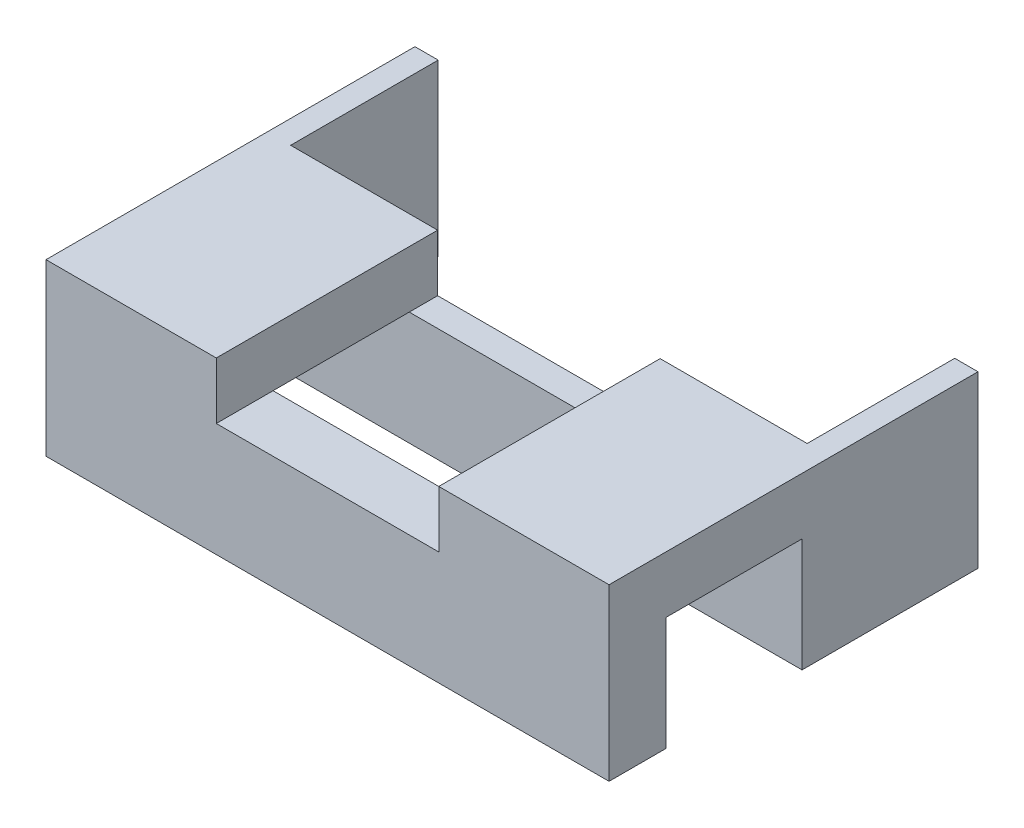
SolidWorks part; units mm, degrees
ref_plane "Front Plane" through (0, 0, 0) normal (0, 0, 1) x (1, 0, 0)
ref_plane "Top Plane" through (0, 0, 0) normal (0, 1, 0) x (1, 0, 0)
ref_plane "Right Plane" through (0, 0, 0) normal (1, 0, 0) x (0, 0, -1)
sketch "Sketch1" plane through (0, 0, 0) normal (0, 1, 0) x (1, 0, 0)
  line L0 (-35, 50) -> (35, 50)
  line L5 (50, 35) -> (50, -35)
  line L6 (-50, 35) -> (-50, -35)
  line L7 (-35, -50) -> (35, -50)
  arc A0 (35, -50) -> (50, -35) centre (35, -35) ccw
  arc A1 (-50, -35) -> (-35, -50) centre (-35, -35) ccw
  arc A2 (-50, 35) -> (-35, 50) centre (-35, 35) cw
  arc A3 (35, 50) -> (50, 35) centre (35, 35) cw
  point P14 (0, -50)
  point P19 (-50, 0)
  dimension "D3" = 15
  dimension "D4" = 15
  dimension "D5" = 15
  dimension "D6" = 15
  dimension "D1" = 100
  dimension "D2" = 100
extrude "Boss-Extrude1" add sketch "Sketch1" along normal blind 10
sketch "Sketch2" plane through (0, 10, 0) normal (0, 1, 0) x (1, 0, 0)
  line L0 (-50, 35) -> (-50, -35) construction
  line L1 (-42, 40) -> (-24.8, 40)
  line L2 (-42, 40) -> (-42, -3)
  line L3 (-42, -3) -> (-24.8, -3)
  line L4 (-24.8, 40) -> (-24.8, -3)
  line L5 (-42, 40) -> (-24.8, -3) construction
  line L6 (-42, -3) -> (-24.8, 40) construction
  line L7 (24.8, 40) -> (42, 40)
  line L8 (24.8, 40) -> (24.8, -3)
  line L9 (24.8, -3) -> (42, -3)
  line L10 (42, 40) -> (42, -3)
  line L11 (24.8, 40) -> (42, -3) construction
  line L12 (24.8, -3) -> (42, 40) construction
  line L13 (50, -35) -> (50, 35) construction
  line L15 (35, 50) -> (-35, 50) construction
  point P0 (-33.4, 18.5)
  point P5 (33.4, 18.5)
  dimension "D1" = 8
  dimension "D2" = 8
  dimension "D3" = 17.2
  dimension "D4" = 17.2
  dimension "D5" = 43
  dimension "D6" = 43
  dimension "D7" = 10
  dimension "D8" = 10
extrude "Cut-Extrude1" cut sketch "Sketch2" against normal through all
sketch "Sketch3" plane through (0, 10, 0) normal (0, 1, 0) x (1, 0, 0)
  line L1 (-40, -8) -> (40, -8)
  line L2 (-40, -8) -> (-40, -32)
  line L3 (-40, -32) -> (40, -32)
  line L4 (40, -8) -> (40, -32)
  line L5 (-40, -8) -> (40, -32) construction
  line L6 (-40, -32) -> (40, -8) construction
  line L7 (-45, -3) -> (45, -3)
  line L8 (-45, -3) -> (-45, -37)
  line L9 (-45, -37) -> (45, -37)
  line L10 (45, -3) -> (45, -37)
  line L11 (-45, -3) -> (45, -37) construction
  line L12 (-45, -37) -> (45, -3) construction
  line L13 (-35, -50) -> (35, -50) construction
  line L14 (-42, -3) -> (-24.8, -3) construction
  point P0 (0, -20)
  point P5 (0, -20)
  point P18 (0, -50)
  dimension "D1" = 24
  dimension "D2" = 80
  dimension "D3" = 34
  dimension "D4" = 90
extrude "Boss-Extrude3" add sketch "Sketch3" along normal blind 15
sketch "Sketch4" plane through (0, 10, 0) normal (0, 1, 0) x (1, 0, 0)
  line L0 (24.8, 40) -> (24.8, -3) construction
  line L3 (-24.8, 12.5) -> (24.8, 12.5)
  line L5 (-24.8, 24.5) -> (24.8, 24.5)
  line L6 (-24.8, 29.5) -> (24.8, 29.5)
  line L11 (-24.8, 7.5) -> (24.8, 7.5)
  line L12 (-24.8, 29.5) -> (-24.8, 24.5)
  line L13 (-24.8, -3) -> (-24.8, 40) construction
  line L14 (-24.8, 12.5) -> (-24.8, 7.5)
  line L15 (24.8, 12.5) -> (24.8, 7.5)
  line L16 (24.8, 29.5) -> (24.8, 24.5)
  point P4 (-24.8, 18.5)
  dimension "D1" = 5
  dimension "D2" = 12
  dimension "D3" = 5
  dimension "D4" = 6
extrude "Boss-Extrude4" add sketch "Sketch4" along normal blind 10
sketch "Sketch5" plane through (0, 20, 0) normal (0, 1, 0) x (1, 0, 0)
  line L0 (-24.8, 7.5) -> (24.8, 7.5) construction
  line L1 (-24.8, 29.5) -> (-9.8, 29.5)
  line L2 (-24.8, 29.5) -> (-24.8, 7.5)
  line L3 (-24.8, 7.5) -> (-9.8, 7.5)
  line L4 (-9.8, 29.5) -> (-9.8, 7.5)
  line L6 (24.8, 29.5) -> (9.8, 29.5)
  line L7 (24.8, 29.5) -> (24.8, 7.5)
  line L8 (24.8, 7.5) -> (9.8, 7.5)
  line L9 (9.8, 29.5) -> (9.8, 7.5)
  dimension "D1" = 15
  dimension "D2" = 15
extrude "Boss-Extrude5" add sketch "Sketch5" along normal blind 5
sketch "Sketch6" plane through (0, 10, 0) normal (0, 1, 0) x (1, 0, 0)
  line L1 (-45, -37) -> (45, -37)
  line L2 (-45, -37) -> (-45, 40)
  line L3 (-45, 40) -> (45, 40)
  line L4 (45, -37) -> (45, 40)
  line L5 (45, -37) -> (45, -3) construction
  line L6 (-24.8, 40) -> (-42, 40) construction
  line L7 (-50, 35) -> (-50, -35) construction
  line L8 (-35, -50) -> (35, -50) construction
  line L9 (50, -35) -> (50, 35) construction
  line L10 (35, 50) -> (-35, 50) construction
  line L11 (-50, 35) -> (-50, -35)
  line L12 (-35, -50) -> (35, -50)
  line L13 (50, -35) -> (50, 35)
  line L14 (35, 50) -> (-35, 50)
  arc A0 (-50, -35) -> (-35, -50) centre (-35, -35) ccw construction
  arc A1 (35, -50) -> (50, -35) centre (35, -35) ccw construction
  arc A2 (50, 35) -> (35, 50) centre (35, 35) ccw construction
  arc A3 (-35, 50) -> (-50, 35) centre (-35, 35) ccw construction
  arc A4 (-50, -35) -> (-35, -50) centre (-35, -35) ccw
  arc A5 (35, -50) -> (50, -35) centre (35, -35) ccw
  arc A6 (50, 35) -> (35, 50) centre (35, 35) ccw
  arc A7 (-35, 50) -> (-50, 35) centre (-35, 35) ccw
extrude "Boss-Extrude6" add sketch "Sketch6" along normal up to surface (15 mm away) up to face at (0, 25, 20)
sketch "Sketch9" plane through (0, 25, 0) normal (0, 1, 0) x (1, 0, 0)
  line L22 (-50, 35) -> (-50, -35) construction
  line L23 (-35, -50) -> (35, -50) construction
  line L24 (50, -35) -> (50, 35) construction
  line L25 (35, 50) -> (-35, 50) construction
  line L26 (-45, 35) -> (-45, -35)
  line L27 (-35, -45) -> (35, -45)
  line L28 (45, -35) -> (45, 35)
  line L29 (35, 45) -> (-35, 45)
  line L30 (-45, 35) -> (-45, -32)
  line L32 (45, -32) -> (45, 35)
  line L34 (-50, 35) -> (-50, -35)
  line L35 (-35, -50) -> (35, -50)
  line L36 (50, -35) -> (50, 35)
  line L37 (35, 50) -> (-35, 50)
  line L38 (45, -32) -> (-45, -32)
  line L39 (-40, -32) -> (40, -32) construction
  line L40 (43.6603, 40) -> (-43.6603, 40)
  line L41 (45, 40) -> (-45, 40) construction
  arc A23 (-50, -35) -> (-35, -50) centre (-35, -35) ccw construction
  arc A24 (35, -50) -> (50, -35) centre (35, -35) ccw construction
  arc A25 (50, 35) -> (35, 50) centre (35, 35) ccw construction
  arc A26 (-35, 50) -> (-50, 35) centre (-35, 35) ccw construction
  arc A27 (-45, -35) -> (-35, -45) centre (-35, -35) ccw
  arc A28 (35, -45) -> (45, -35) centre (35, -35) ccw
  arc A29 (45, 35) -> (35, 45) centre (35, 35) ccw
  arc A30 (-35, 45) -> (-45, 35) centre (-35, 35) ccw
  arc A33 (45, 35) -> (43.6603, 40) centre (35, 35) ccw
  arc A34 (-43.6603, 40) -> (-45, 35) centre (-35, 35) ccw
  arc A35 (-50, -35) -> (-35, -50) centre (-35, -35) ccw
  arc A36 (35, -50) -> (50, -35) centre (35, -35) ccw
  arc A37 (50, 35) -> (35, 50) centre (35, 35) ccw
  arc A38 (-35, 50) -> (-50, 35) centre (-35, 35) ccw
  dimension "D1" = 5
extrude "Boss-Extrude8" add sketch "Sketch9" along normal blind 39
chamfer "Chamfer1" distance 64 angle 3 8 edges at (0, 64, 50) (45.6066, 64, 45.6066) (-45.6066, 64, 45.6066) (50, 64, 0) (-50, 64, 0) (45.6066, 64, -45.6066) (-45.6066, 64, -45.6066) (0, 64, -50) first distance on face at (0, 32, 50) first distance on face at (44.0533, 32, 44.0533) first distance on face at (-44.0533, 32, 44.0533) first distance on face at (50, 32, 0) first distance on face at (-50, 32, 0) first distance on face at (44.0533, 32, -44.0533) first distance on face at (-44.0533, 32, -44.0533) first distance on face at (0, 32, -50)
chamfer "Chamfer2" distance 64 angle 10 1 edges at (0, 64, -46.6459) tangent propagation no first distance on face at (0, 32, -48.323)
chamfer "Chamfer3" distance 64 angle 12 1 edges at (0, 64, 46.6459) tangent propagation no first distance on face at (0, 32, 48.323)
sketch "Sketch10" plane through (0, 1.3075, 0) normal (-1, 0, 0) x (0, 0, 1)
  line L0 (-35, 62.6925) -> (32.8702, 62.6925) construction
  line L1 (2.8702, 62.6925) -> (-47.1298, 62.6925)
  line L2 (2.8702, 62.6925) -> (2.8702, 35.6925)
  line L3 (2.8702, 35.6925) -> (-47.1298, 35.6925)
  line L4 (-47.1298, 62.6925) -> (-47.1298, 35.6925)
  dimension "D1" = 50
  dimension "D2" = 27
  dimension "D3" = 30
extrude "Cut-Extrude3" cut sketch "Sketch10" against normal through all and the other way through all
sketch "Sketch15" plane through (0, 0, -40) normal (0, 0, 1) x (1, 0, 0)
  line L1 (12.75, 20.25) -> (-12.75, 20.25) construction
  line L2 (0, -35.2) -> (0, 35.2) construction
  line L3 (24.8, 10) -> (-24.8, 10) construction
  circle A0 centre (-12.75, 20.25) radius 8
  circle A1 centre (12.75, 20.25) radius 8
  point P9 (0, 20.25)
  dimension "D3" = 16
  dimension "D4" = 16
  dimension "D1" = 10.25
  dimension "D5" = 25.5
extrude "Cut-Extrude5" cut sketch "Sketch15" against normal through all
sketch "Sketch17" plane through (0, 0, -29.5) normal (0, 0, -1) x (-1, 0, 0)
  line L8 (-9.8, 25) -> (-24.8, 25)
  line L9 (-24.8, 10) -> (24.8, 10)
  line L10 (-24.8, 10) -> (24.8, 10)
  line L11 (24.8, 10) -> (24.8, 25)
  line L12 (24.8, 25) -> (9.8, 25)
  line L13 (9.8, 25) -> (9.8, 20)
  line L14 (9.8, 20) -> (-9.8, 20)
  line L15 (-9.8, 20) -> (-9.8, 25)
  line L16 (-9.8, 25) -> (-24.8, 25)
  line L20 (24.8, 25) -> (9.8, 25)
  line L21 (9.8, 25) -> (9.8, 20)
  line L22 (9.8, 20) -> (-9.8, 20)
  line L23 (-9.8, 20) -> (-9.8, 25)
  line L24 (24.8, 10) -> (24.8, 25)
  line L25 (-24.8, 25) -> (-24.8, 10)
  line L26 (-24.8, 25) -> (-24.8, 10)
  dimension "D1" = 0
extrude "Cut-Extrude6" cut sketch "Sketch17" against normal blind 2.5
sketch "Sketch18" plane through (0, 0, 0) normal (0, -1, 0) x (1, 0, 0)
  line L0 (-24.8, -40) -> (-42, -40) construction
  line L1 (-14.8, -40) -> (14.8, -40)
  line L2 (-14.8, -40) -> (-14.8, 3)
  line L3 (-14.8, 3) -> (14.8, 3)
  line L4 (14.8, -40) -> (14.8, 3)
  line L5 (-24.8, 3) -> (-24.8, -40) construction
  line L6 (24.8, -40) -> (24.8, 3) construction
  line L7 (24.8, 3) -> (42, 3) construction
  dimension "D1" = 10
  dimension "D2" = 10
extrude "Cut-Extrude7" cut sketch "Sketch18" against normal up to surface (10 mm away) up to face at (0, 10, -18.5)
sketch "Sketch20" plane through (0, 25, 0) normal (0, -1, 0) x (1, 0, 0)
  line L0 (-45, -35) -> (-45, -40) construction
  line L1 (-45, -40) -> (-43.6603, -40) construction
  line L2 (45, -40) -> (45, -35) construction
  line L3 (43.6603, -40) -> (45, -40) construction
  line L4 (-45, -35) -> (-45, -40)
  line L5 (-45, -40) -> (-43.6603, -40)
  line L6 (45, -40) -> (45, -35)
  line L7 (43.6603, -40) -> (45, -40)
  arc A0 (-45, -35) -> (-43.6603, -40) centre (-35, -35) ccw construction
  arc A1 (43.6603, -40) -> (45, -35) centre (35, -35) ccw construction
  arc A2 (-45, -35) -> (-43.6603, -40) centre (-35, -35) ccw
  arc A3 (43.6603, -40) -> (45, -35) centre (35, -35) ccw
extrude "Cut-Extrude8" cut sketch "Sketch20" against normal blind 15
sketch "Sketch21" plane through (0, 0, 0) normal (0, -1, 0) x (1, 0, 0)
  line L0 (-14.8, 3) -> (-14.8, -40) construction
  line L1 (-14.8, 3) -> (14.8, 3)
  line L2 (-14.8, 3) -> (-14.8, -30)
  line L3 (-14.8, -30) -> (14.8, -30)
  line L4 (14.8, 3) -> (14.8, -30)
  line L5 (14.8, -40) -> (14.8, 3) construction
  line L7 (-14.8, -40) -> (14.8, -40) construction
  line L8 (14.8, 3) -> (-14.8, 3) construction
  dimension "D2" = 10
extrude "Boss-Extrude10" add sketch "Sketch21" against normal blind 2.5
sketch "Sketch23" plane through (0, 10, 0) normal (0, 1, 0) x (1, 0, 0)
  line L0 (-24.8, 27) -> (-9.8, 27) construction
  line L2 (-22.75, 27) -> (-22.75, 40)
  line L4 (22.75, 27) -> (22.75, 40)
  line L5 (24.8, 40) -> (14.8, 40) construction
  line L6 (-24.8, 27) -> (-24.8, 40) construction
  line L7 (24.8, 40) -> (24.8, 27) construction
  line L8 (24.8, 40) -> (24.8, 27)
  line L9 (-24.8, 27) -> (-24.8, 40)
  line L10 (-22.75, 27) -> (-24.8, 27)
  line L11 (22.75, 27) -> (24.8, 27)
  line L12 (24.8, 40) -> (22.75, 40)
  line L13 (-22.75, 40) -> (-24.8, 40)
  dimension "D1" = 45.5
  dimension "D2" = 2.05
extrude "Boss-Extrude11" add sketch "Sketch23" along normal up to surface (15 mm away) up to face at (-17.3, 25, -17.25)
sketch "Sketch24" plane through (0, 64, 0) normal (0, 1, 0) x (1, 0, 0)
  line L1 (-45, -32) -> (45, -32)
  line L2 (-45, -32) -> (-45, 40)
  line L3 (-45, 40) -> (45, 40)
  line L4 (45, -32) -> (45, 40)
extrude "Cut-Extrude10" cut sketch "Sketch24" against normal up to surface (61.5 mm away) flip side to cut contours L2 L3 L4 L1 up to face at (0, 2.5, -13.5)
sketch "Sketch26" plane through (0, 0, 0) normal (0, -1, 0) x (1, 0, 0)
  line L0 (-50, -35) -> (-50, 35) construction
  line L1 (-50, 50) -> (50, 50)
  line L2 (-50, 50) -> (-50, -50)
  line L3 (-50, -50) -> (50, -50)
  line L4 (50, 50) -> (50, -50)
  line L5 (35, -50) -> (-35, -50) construction
  line L6 (50, 35) -> (50, -35) construction
  line L7 (-35, 50) -> (35, 50) construction
extrude "Cut-Extrude13" cut sketch "Sketch26" against normal up to surface (10 mm away) up to face at (-19.8, 10, -2.25)
